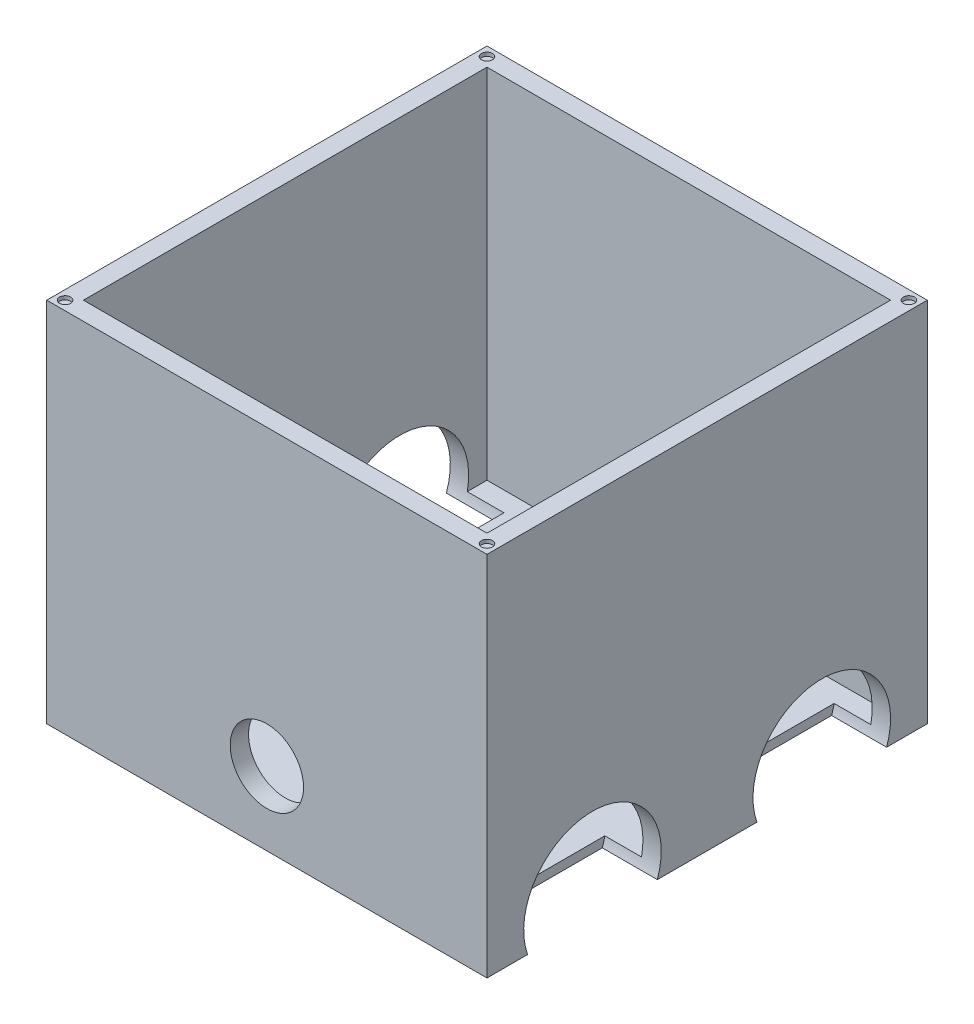
SolidWorks part; units mm, degrees
ref_plane "Front Plane" through (0, 0, 0) normal (0, 0, 1) x (1, 0, 0)
ref_plane "Top Plane" through (0, 0, 0) normal (0, 1, 0) x (1, 0, 0)
ref_plane "Right Plane" through (0, 0, 0) normal (1, 0, 0) x (0, 0, -1)
sketch "Sketch2" plane through (0, -113.102, 0) normal (0, 1, 0) x (1, 0, 0)
  line L1 (-120, -120) -> (120, -120)
  line L2 (-120, -120) -> (-120, 120)
  line L3 (-120, 120) -> (120, 120)
  line L4 (120, -120) -> (120, 120)
  line L5 (-120, -120) -> (120, 120) construction
  line L6 (-120, 120) -> (120, -120) construction
  point P0 (0, 0)
  dimension "D1" = 240
  dimension "D2" = 240
extrude "Boss-Extrude1" add sketch "Sketch2" along normal blind 200
sketch "Sketch17" plane through (0, 86.898, 0) normal (0, 1, 0) x (1, 0, 0)
  line L0 (-110, -110) -> (-110, 110)
  line L1 (-110, 110) -> (110, 110)
  line L2 (110, 110) -> (110, -110)
  line L3 (110, -110) -> (-110, -110)
  line L4 (-120, -120) -> (120, -120) construction
  line L6 (-120, 120) -> (-120, -120) construction
  point P4 (-110, 0)
  dimension "D1" = 220
  dimension "D2" = 10
  dimension "D3" = 220
  dimension "D4" = 10
extrude "Cut-Extrude1" cut sketch "Sketch17" against normal blind 195
sketch "Sketch18" plane through (0, 0, 120) normal (0, 0, 1) x (1, 0, 0)
  line L0 (120, 86.898) -> (120, -113.102) construction
  line L1 (-120, -113.102) -> (120, -113.102) construction
  circle A0 centre (0, -73.102) radius 20
  dimension "D1" = 40
  dimension "D2" = 120
  dimension "D3" = 40
extrude "Cut-Extrude2" cut sketch "Sketch18" against normal blind 10
sketch "Sketch20" plane through (120, 0, 0) normal (1, 0, 0) x (0, 0, -1)
  line L0 (-120, 86.898) -> (-120, -113.102) construction
  line L1 (120, 86.898) -> (120, -113.102) construction
  line L2 (-120, -113.102) -> (120, -113.102) construction
  circle A0 centre (-62.5, -100.602) radius 37.5
  circle A1 centre (62.5, -100.602) radius 37.5
  point P6 (-100, -100.602)
  point P7 (100, -100.602)
  dimension "D1" = 75
  dimension "D2" = 75
  dimension "D3" = 20
  dimension "D4" = 20
  dimension "D5" = 12.5
  dimension "D6" = 12.5
extrude "Cut-Extrude3" cut sketch "Sketch20" against normal blind 30
sketch "Sketch21" plane through (-120, 0, 0) normal (-1, 0, 0) x (0, 0, 1)
  line L0 (-120, 86.898) -> (-120, -113.102) construction
  line L1 (120, 86.898) -> (120, -113.102) construction
  line L2 (-120, -113.102) -> (120, -113.102) construction
  circle A0 centre (62.5, -100.602) radius 37.5
  circle A1 centre (-62.5, -100.602) radius 37.5
  point P4 (-100, -100.602)
  point P5 (100, -100.602)
  dimension "D5" = 75
  dimension "D6" = 75
  dimension "D1" = 20
  dimension "D2" = 20
  dimension "D3" = 12.5
  dimension "D4" = 12.5
extrude "Cut-Extrude4" cut sketch "Sketch21" against normal blind 30
sketch "Sketch22" plane through (0, 86.898, 0) normal (0, 1, 0) x (1, 0, 0)
  line L0 (-120, 120) -> (-120, -120) construction
  line L1 (120, 120) -> (-120, 120) construction
  line L4 (-110, 0) -> (110, 0) construction
  line L7 (0, -110) -> (0, 110) construction
  circle A0 centre (-115, 115) radius 3
  circle A1 centre (-115, -115) radius 3
  circle A2 centre (115, -115) radius 3
  circle A3 centre (115, 115) radius 3
  point P4 (0, 0)
  dimension "D1" = 6
  dimension "D2" = 5
  dimension "D3" = 5
extrude "Cut-Extrude5" cut sketch "Sketch22" against normal blind 2
